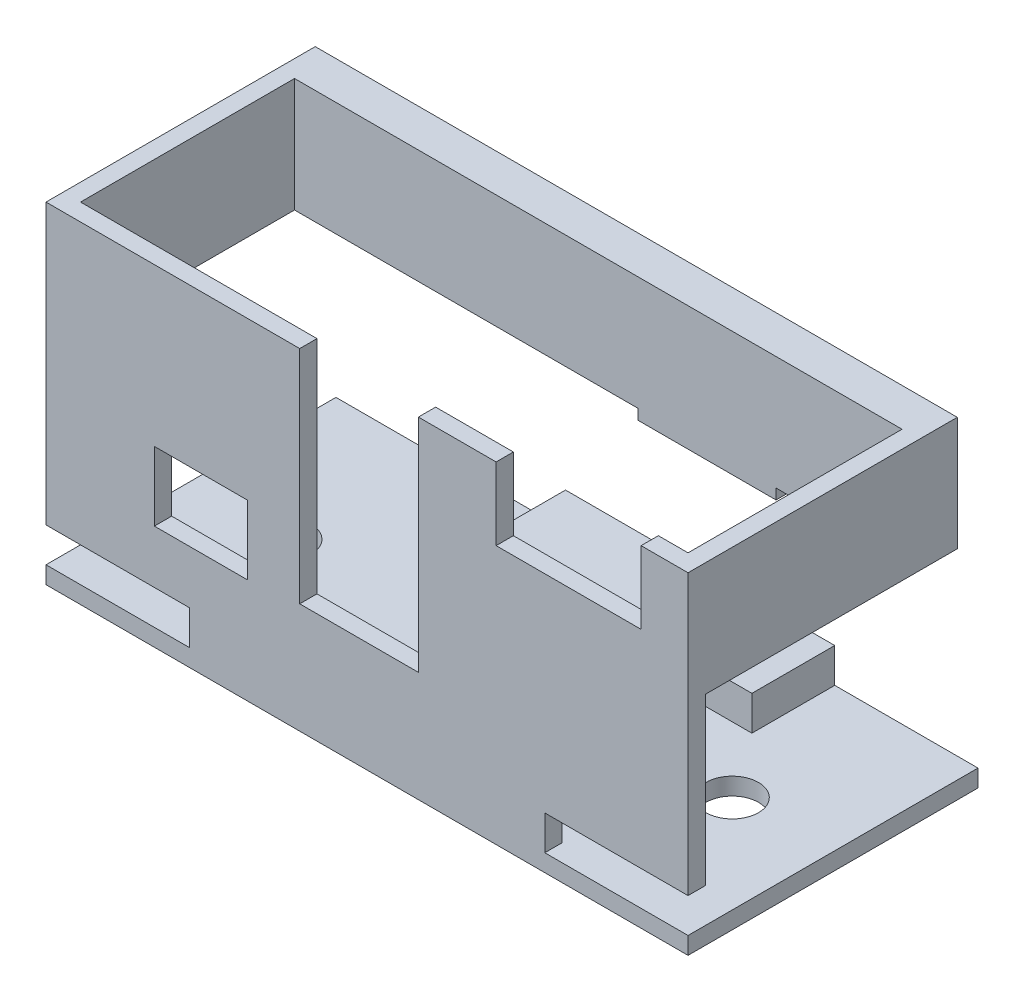
SolidWorks part; units mm, degrees
ref_plane "Front" through (0, 0, 0) normal (0, 0, 1) x (1, 0, 0)
ref_plane "Top" through (0, 0, 0) normal (0, 1, 0) x (1, 0, 0)
ref_plane "Right" through (0, 0, 0) normal (1, 0, 0) x (0, 0, -1)
sketch "Sketch1" plane through (0, 0, 0) normal (0, 0, 1) x (1, 0, 0)
  line L0 (-1.25, 0) -> (-1.25, 24)
  line L1 (-1.25, 0) -> (45.25, 0)
  line L2 (0, 0) -> (0, 22.75) construction
  line L3 (-1.25, 22.75) -> (45.25, 22.75) construction
  line L4 (44, 0) -> (44, 22.75) construction
  line L5 (45.25, 0) -> (45.25, 24)
  line L6 (-1.25, 24) -> (45.25, 24)
  line L7 (-1.25, 0) -> (-1.25, 22.75) construction
  line L8 (45.25, 0) -> (45.25, 22.75) construction
  dimension "D1" = 44
  dimension "D2" = 22.75
  dimension "D5" = 46.5
  dimension "D3" = 1.25
  dimension "D4" = 1.25
  dimension "D6" = 1.25
extrude "Boss-Extrude1" add sketch "Sketch1" against normal blind 21
shell "Shell1" thickness 1.25 removed face at (22, 24, -10.5) removed face at (22, 12, -21)
sketch "Sketch2" plane through (-1.25, 0, 0) normal (-1, 0, 0) x (0, 0, 1)
  line L0 (-1.25, 24) -> (-1.25, 1.25) construction
  line L1 (-21, 1.25) -> (-1.25, 1.25)
  line L2 (-21, 1.25) -> (-21, 15.75)
  line L3 (-21, 15.75) -> (-1.25, 15.75)
  line L4 (-1.25, 1.25) -> (-1.25, 15.75)
  dimension "D1" = 14.5
extrude "Cut-Extrude1" cut sketch "Sketch2" against normal through all
sketch "Sketch6" plane through (0, 0, 0) normal (0, -1, 0) x (-1, 0, 0)
  circle A0 centre (-38.2, 10.25) radius 2.875 construction
  circle A1 centre (-5.8, 10.25) radius 4.25 construction
  circle A2 centre (-5.8, 10.25) radius 4.25 construction
  circle A4 centre (-5.8, 10.25) radius 1.75 construction
  circle A5 centre (-5.8, 10.25) radius 1.75 construction
  circle A6 centre (-5.8, 10.25) radius 1.9
  circle A7 centre (-38.2, 10.25) radius 2.875 construction
  circle A8 centre (-38.2, 10.25) radius 1.75 construction
  circle A9 centre (-38.2, 10.25) radius 1.9
  circle A10 centre (-38.2, 10.25) radius 1.75 construction
  dimension "D1" = 0.15
  dimension "D3" = 0.15
sketch "Sketch7" plane through (0, 0, 0) normal (0, 0, 1) x (1, 0, 0)
  line L0 (45.25, 0) -> (45.25, 24) construction
  line L1 (45.25, 1.25) -> (34.875, 1.25)
  line L2 (45.25, 1.25) -> (45.25, 3.75)
  line L3 (45.25, 3.75) -> (34.875, 3.75)
  line L4 (34.875, 1.25) -> (34.875, 3.75)
  line L5 (-1.25, 0) -> (45.25, 0) construction
  line L7 (35.925, 0) -> (39.825, 0) construction
  line L8 (37.875, 0) -> (37.875, 1.5787) construction
  line L9 (22, 0) -> (22, 4.652) construction
  line L10 (9.125, 1.25) -> (9.125, 3.75)
  line L11 (-1.25, 3.75) -> (9.125, 3.75)
  line L12 (-1.25, 1.25) -> (-1.25, 3.75)
  line L13 (-1.25, 1.25) -> (9.125, 1.25)
  dimension "D1" = 1.25
  dimension "D2" = 3
  dimension "D3" = 2.5
extrude "Cut-Extrude5" cut sketch "Sketch7" against normal up to surface (1.25 mm away) up to face at (22, 14.1875, -1.25)
sketch "Sketch9" plane through (0, 1.25, 0) normal (0, 1, 0) x (1, 0, 0)
  line L0 (-1.25, 21) -> (45.25, 21) construction
  line L1 (34.875, 21) -> (15.375, 21)
  line L2 (34.875, 21) -> (34.875, 15)
  line L3 (34.875, 15) -> (15.375, 15)
  line L4 (15.375, 21) -> (15.375, 15)
  line L6 (34.875, 1.25) -> (34.875, 21) construction
  dimension "D1" = 6
  dimension "D2" = 19.5
extrude "Boss-Extrude3" add sketch "Sketch9" along normal blind 2.5
sketch "Sketch12" plane through (45.25, 0, 0) normal (1, 0, 0) x (0, 0, -1)
  line L1 (1.25, 15.75) -> (21, 15.75) construction
  line L2 (21, 24) -> (19.5, 24)
  line L3 (21, 24) -> (21, 15.75)
  line L4 (21, 15.75) -> (19.5, 15.75)
  line L5 (19.5, 24) -> (19.5, 15.75)
  dimension "D1" = 1.5
extrude "Cut-Extrude7" cut sketch "Sketch12" along normal through all and the other way through all from surface starting at face at (0, 19.875, -11.125)
sketch "Sketch13" plane through (0, 0, 0) normal (1, 0, 0) x (0, 0, -1)
  line L0 (1.25, 15.75) -> (19.5, 15.75) construction
  line L1 (19.5, 24) -> (16.75, 24)
  line L2 (19.5, 24) -> (19.5, 15.75)
  line L3 (19.5, 15.75) -> (16.75, 15.75)
  line L4 (16.75, 24) -> (16.75, 15.75)
  dimension "D1" = 2.75
extrude "Boss-Extrude4" add sketch "Sketch13" along normal up to vertex (44 mm away) contours L4 L3 L2 L1 up to point (44, 24, -19.5)
sketch "Sketch15" plane through (0, 15.75, 0) normal (0, -1, 0) x (1, 0, 0)
  line L0 (-1.25, -19.5) -> (45.25, -19.5) construction
  line L1 (34.875, -19.5) -> (24.875, -19.5)
  line L2 (34.875, -19.5) -> (34.875, -16.75)
  line L3 (34.875, -16.75) -> (24.875, -16.75)
  line L4 (24.875, -19.5) -> (24.875, -16.75)
  line L5 (44, -16.75) -> (0, -16.75) construction
  line L6 (34.875, -15) -> (34.875, -21) construction
  dimension "D1" = 10
extrude "Boss-Extrude5" add sketch "Sketch15" along normal blind 0.75 contours L1 L4 L3 L2
sketch "Sketch17" plane through (0, 0, -2.75) normal (0, 0, 1) x (1, 0, 0)
  line L4 (8.1, 8.6) -> (11.86, 8.6)
  line L5 (8.1, 11.6) -> (8.1, 8.6)
  line L6 (11.86, 11.6) -> (8.1, 11.6)
  line L7 (11.86, 8.6) -> (11.86, 11.6)
  line L8 (8.1, 8.6) -> (11.86, 8.6)
  line L9 (8.1, 11.6) -> (8.1, 8.6)
  line L10 (11.86, 11.6) -> (8.1, 11.6)
  line L11 (11.86, 8.6) -> (11.86, 11.6)
  line L12 (19.1256, 9.4882) -> (23.7194, 9.4882)
  line L13 (23.7194, 9.4882) -> (23.7194, 14.357)
  line L14 (23.7194, 14.357) -> (19.1256, 14.357)
  line L15 (19.1256, 14.357) -> (19.1256, 9.4882)
  line L16 (19.1256, 9.4882) -> (23.7194, 9.4882)
  line L17 (23.7194, 9.4882) -> (23.7194, 14.357)
  line L18 (23.7194, 14.357) -> (19.1256, 14.357)
  line L19 (19.1256, 14.357) -> (19.1256, 9.4882)
  dimension "D1" = 0
  dimension "D2" = 0
sketch "Sketch18" plane through (0, 0, 0) normal (0, 0, 1) x (1, 0, 0)
  line L0 (8.1, 11.6) -> (8.1, 8.6) construction
  line L1 (6.6, 12.6) -> (13.36, 12.6)
  line L2 (6.6, 12.6) -> (6.6, 7.6)
  line L3 (6.6, 7.6) -> (13.36, 7.6)
  line L4 (13.36, 12.6) -> (13.36, 7.6)
  line L5 (11.86, 11.6) -> (8.1, 11.6) construction
  line L6 (11.86, 8.6) -> (11.86, 11.6) construction
  line L7 (8.1, 8.6) -> (11.86, 8.6) construction
  dimension "D1" = 1.5
  dimension "D2" = 1
  dimension "D3" = 1.5
  dimension "D4" = 1
extrude "Cut-Extrude8" cut sketch "Sketch18" against normal up to next
sketch "Sketch22" plane through (0, 0, 0) normal (0, 0, 1) x (1, 0, 0)
  line L0 (45.25, 24) -> (-1.25, 24) construction
  line L1 (17.1256, 24) -> (25.7194, 24)
  line L2 (17.1256, 24) -> (17.1256, 7.9882)
  line L3 (17.1256, 7.9882) -> (25.7194, 7.9882)
  line L4 (25.7194, 24) -> (25.7194, 7.9882)
  line L5 (19.1256, 14.357) -> (19.1256, 9.4882) construction
  line L6 (23.7194, 9.4882) -> (23.7194, 14.357) construction
  line L7 (19.1256, 9.4882) -> (23.7194, 9.4882) construction
  dimension "D1" = 2
  dimension "D2" = 2
  dimension "D3" = 1.5
extrude "Cut-Extrude9" cut sketch "Sketch22" against normal up to next
ref_plane "Plane1" through (41.175, 19.5, -0.25) normal (1, 0, 0) x (0, -1, 0)
sketch "Sketch25" plane through (0, 0, 0) normal (0, 0, 1) x (1, 0, 0)
  line L1 (41.85, 18.75) -> (31.35, 18.75)
  line L2 (41.85, 18.75) -> (41.85, 24)
  line L3 (41.85, 24) -> (31.35, 24)
  line L4 (31.35, 18.75) -> (31.35, 24)
  line L16 (17.1256, 7.9882) -> (17.1256, 24)
  line L17 (17.1256, 24) -> (-1.25, 24)
  line L18 (-1.25, 24) -> (-1.25, 3.75)
  line L23 (-1.25, 0) -> (45.25, 0)
  line L24 (45.25, 0) -> (45.25, 1.25)
  line L25 (-1.25, 3.75) -> (9.125, 3.75)
  line L26 (-1.25, 3.75) -> (9.125, 3.75)
  line L27 (9.125, 3.75) -> (9.125, 1.25)
  line L28 (9.125, 3.75) -> (9.125, 1.25)
  line L29 (45.25, 24) -> (25.7194, 24)
  line L30 (25.7194, 24) -> (25.7194, 7.9882)
  line L31 (25.7194, 7.9882) -> (17.1256, 7.9882)
  line L32 (17.1256, 7.9882) -> (17.1256, 24)
  line L33 (17.1256, 24) -> (-1.25, 24)
  line L34 (-1.25, 24) -> (-1.25, 3.75)
  line L35 (9.125, 1.25) -> (-1.25, 1.25)
  line L36 (9.125, 1.25) -> (-1.25, 1.25)
  line L37 (-1.25, 1.25) -> (-1.25, 0)
  line L38 (-1.25, 1.25) -> (-1.25, 0)
  line L39 (-1.25, 0) -> (45.25, 0)
  line L40 (45.25, 0) -> (45.25, 1.25)
  line L41 (45.25, 1.25) -> (34.875, 1.25)
  line L42 (45.25, 1.25) -> (34.875, 1.25)
  line L43 (34.875, 1.25) -> (34.875, 3.75)
  line L44 (34.875, 1.25) -> (34.875, 3.75)
  line L45 (45.25, 24) -> (25.7194, 24)
  line L46 (25.7194, 24) -> (25.7194, 7.9882)
  line L47 (25.7194, 7.9882) -> (17.1256, 7.9882)
  line L48 (34.875, 3.75) -> (45.25, 3.75)
  line L49 (34.875, 3.75) -> (45.25, 3.75)
  line L50 (45.25, 3.75) -> (45.25, 24)
  line L51 (45.25, 3.75) -> (45.25, 24)
  line L52 (31.6, 24) -> (31.6, 19.5)
  line L53 (31.6, 19.5) -> (41.6, 19.5)
  line L54 (41.6, 19.5) -> (41.6, 24)
  line L55 (41.6, 24) -> (31.6, 24)
  line L56 (31.6, 24) -> (31.6, 19.5)
  line L57 (31.6, 19.5) -> (41.6, 19.5)
  line L58 (41.6, 19.5) -> (41.6, 24)
  line L59 (41.6, 24) -> (31.6, 24)
  line M34 (45.25, 24) -> (25.7194, 24)
  dimension "D3" = 0.25
  dimension "D4" = 0.75
  dimension "D5" = 0.25
  dimension "D1" = 0
  dimension "D2" = 0
extrude "Cut-Extrude15" cut sketch "Sketch25" against normal up to next contours L58 L57 L56 L45 L4 L1 L2 M34 | L57 L58 L45 L56 region at (36.6, 18.8674, 0) region at (36.6, 21.75, 0)
extrude "Cut-Extrude16" cut sketch "Sketch6" against normal up to next
